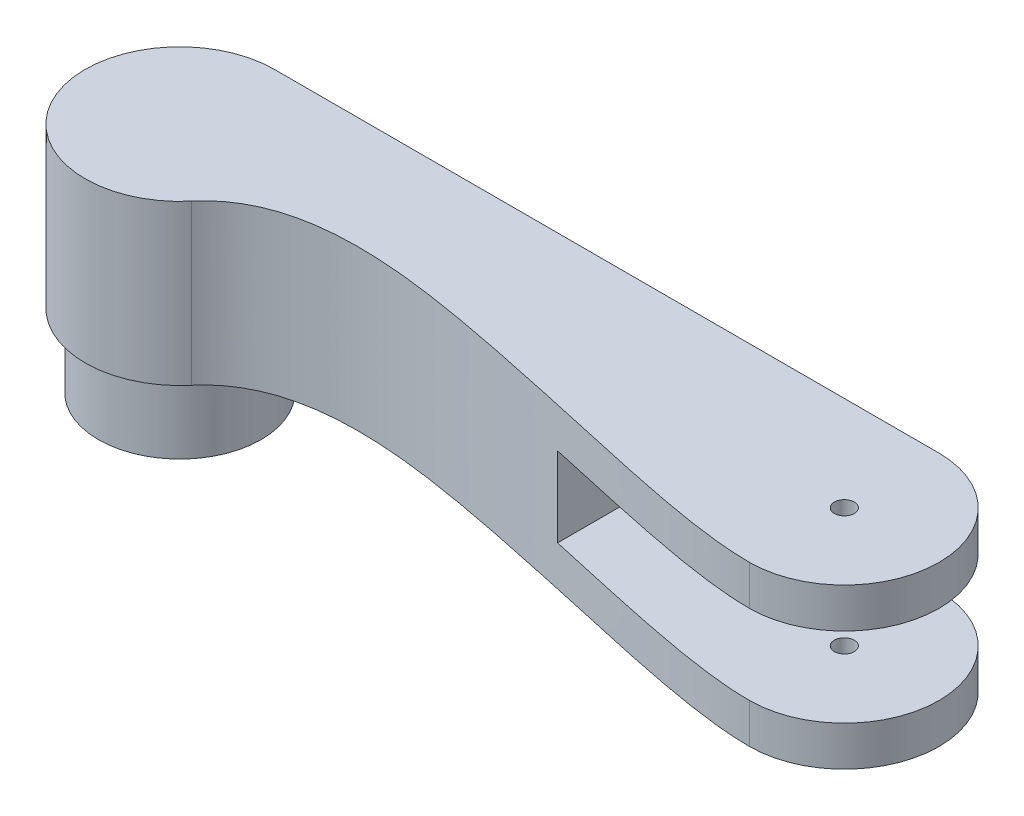
SolidWorks part; units mm, degrees
ref_plane "Front Plane" through (0, 0, 0) normal (0, 0, 1) x (1, 0, 0)
ref_plane "Top Plane" through (0, 0, 0) normal (0, 1, 0) x (1, 0, 0)
ref_plane "Right Plane" through (0, 0, 0) normal (1, 0, 0) x (0, 0, -1)
sketch "Sketch1" plane through (0, 0, 0) normal (0, 1, 0) x (1, 0, 0)
  line L0 (-50, 0) -> (50, 0) construction
  line L1 (-50, 14.25) -> (50, 14.25)
  line L2 (-50, -14.25) -> (50, -14.25)
  arc A0 (-50, 14.25) -> (-50, -14.25) centre (-50, 0) ccw
  arc A1 (50, -14.25) -> (50, 14.25) centre (50, 0) ccw
  point P3 (0, 0)
  dimension "D1" = 14.25
  dimension "D2" = 100
extrude "Boss-Extrude1" add sketch "Sketch1" along normal blind 6
sketch "Sketch3" plane through (0, 0, 0) normal (0, -1, 0) x (1, 0, 0)
  circle A0 centre (50, 0) radius 1.5
  dimension "D1" = 3
extrude "Cut-Extrude2" cut sketch "Sketch3" against normal through all
sketch "Sketch4" plane through (0, 6, 0) normal (0, 1, 0) x (1, 0, 0)
  line L0 (-50, 14.25) -> (15, 14.25)
  line L1 (-50, 14.25) -> (50, 14.25) construction
  line L2 (15, 14.25) -> (15, -14.25)
  line L3 (-50, -14.25) -> (50, -14.25) construction
  line L4 (15, -14.25) -> (-50, -14.25)
  arc A0 (-50, 14.25) -> (-50, -14.25) centre (-50, 0) ccw
  arc A1 (-50, 14.25) -> (-50, -14.25) centre (-50, 0) ccw construction
  dimension "D1" = 65
extrude "Boss-Extrude2" add sketch "Sketch4" along normal blind 12
sketch "Sketch5" plane through (0, 18, 0) normal (0, 1, 0) x (1, 0, 0)
  line L0 (-50, 0) -> (50, 0) construction
  line L1 (-50, 14.25) -> (50, 14.25)
  line L2 (-50, -14.25) -> (50, -14.25)
  arc A0 (-50, 14.25) -> (-50, -14.25) centre (-50, 0) ccw
  arc A1 (50, -14.25) -> (50, 14.25) centre (50, 0) ccw
  point P4 (0, 0)
  dimension "D1" = 14.25
extrude "Boss-Extrude3" add sketch "Sketch5" along normal blind 6
sketch "Sketch6" plane through (0, 24, 0) normal (0, 1, 0) x (1, 0, 0)
  circle A0 centre (50, 0) radius 1.5
  dimension "D1" = 3
extrude "Cut-Extrude3" cut sketch "Sketch6" against normal up to next
sketch "Sketch7" plane through (0, 24, 0) normal (0, 1, 0) x (1, 0, 0)
  line L0 (0, -13.2) -> (0, 13.2) construction
  line L1 (-50, -14.25) -> (50, -14.25)
  circle A0 centre (-50, 0) radius 14.25
  circle A1 centre (50, 0) radius 14.25
  spline S0 degree 3 poles (-39.0732, -9.1469) (-31.5141, -0.117) (5.4387, -4.6452) (38.6975, -14.25) (50, -14.25) knots 0 0 0 0 0.435908 1 1 1 1
  line M5 (-50, -14.25) -> (50, -14.25)
extrude "Cut-Extrude4" cut sketch "Sketch7" against normal up to next contours S0 A0 M5 region at (-8.5907, 24, 9.7914)
sketch "Sketch8" plane through (0, 0, 0) normal (0, -1, 0) x (1, 0, 0)
  circle A1 centre (-50, 0) radius 12.25
  dimension "D1" = 24.5
extrude "Boss-Extrude4" add sketch "Sketch8" along normal blind 11
sketch "Sketch9" plane through (0, -11, 0) normal (0, -1, 0) x (1, 0, 0)
  circle A0 centre (-50, 0) radius 8.25 construction
  circle A1 centre (-50, 8.25) radius 2.5
  circle A2 centre (-50, -8.25) radius 2.5
  arc A3 (-50, 14.25) -> (-50, -14.25) centre (-50, 0) ccw construction
  point P6 (-50, 0)
  point P7 (0, 0)
  dimension "D1" = 16.5
  dimension "D2" = 5
extrude "Cut-Extrude5" cut sketch "Sketch9" against normal blind 6
equation "\"Length\"= 100mm"
equation "\"Radius\"= 14.25mm"
equation "\"Thick\"= 12mm"
equation "\"D1@Sketch1\"= \"Radius\""
equation "\"D2@Sketch1\" = \"Length\""
equation "\"D1@Boss-Extrude1\"= \"Thick\""
equation "\"D1@Sketch4\"=\"Length\"*0.65"
equation "\"D1@Sketch5\"=\"Radius\""
equation "\"D1@Boss-Extrude2\"=\"Thick\""
equation "\"D1@Boss-Extrude4\"=\"Thick\"-1"
